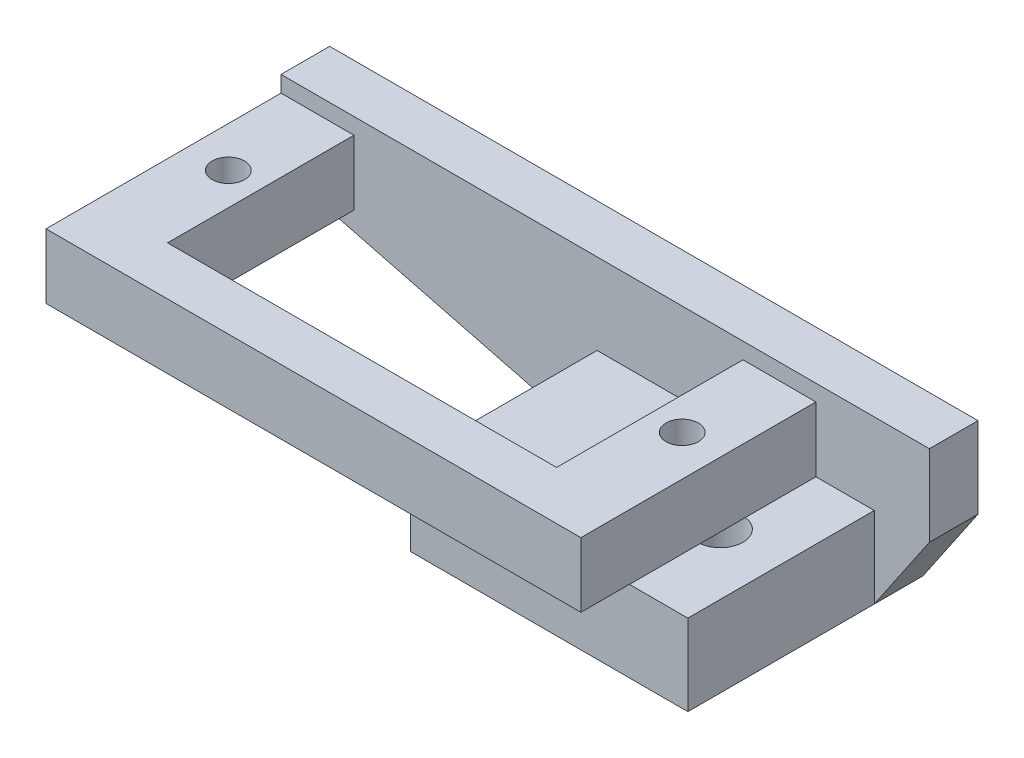
SolidWorks part; units mm, degrees
ref_plane "Спереди" through (0, 0, 0) normal (0, 0, 1) x (1, 0, 0)
ref_plane "Сверху" through (0, 0, 0) normal (0, 1, 0) x (1, 0, 0)
ref_plane "Справа" through (0, 0, 0) normal (1, 0, 0) x (0, 0, -1)
sketch "Эскиз1" plane through (0, 0, 0) normal (0, 0, 1) x (1, 0, 0)
  line L1 (-20, -2.5) -> (20, -2.5)
  line L2 (-20, -2.5) -> (-20, 2.5)
  line L3 (-20, 2.5) -> (20, 2.5)
  line L4 (20, -2.5) -> (20, 2.5)
  line L5 (-20, -2.5) -> (20, 2.5) construction
  line L6 (-20, 2.5) -> (20, -2.5) construction
  point P0 (0, 0)
  dimension "D1" = 40
  dimension "D2" = 5
extrude "Бобышка-Вытянуть1" add sketch "Эскиз1" along normal blind 3
sketch "Эскиз2" plane through (0, 0, 3) normal (0, 0, 1) x (1, 0, 0)
  line L5 (-20, -2.5) -> (-15.5, -2.5)
  line L6 (-20, -2.5) -> (-20, 1.5)
  line L11 (-20, 1.5) -> (-15.5, 1.5)
  line L12 (-15.5, -2.5) -> (-15.5, 1.5)
  line L13 (8.5, -2.5) -> (13, -2.5)
  line L14 (8.5, -2.5) -> (8.5, 1.5)
  line L15 (8.5, 1.5) -> (13, 1.5)
  line L16 (13, -2.5) -> (13, 1.5)
  line L17 (-20, 2.5) -> (-20, -2.5) construction
  point P8 (-20, -7.5)
  dimension "D2" = 24
  dimension "D3" = 4.5
  dimension "D4" = 4.5
  dimension "D5" = 4
extrude "Бобышка-Вытянуть2" add sketch "Эскиз2" along normal blind 11.5
sketch "Эскиз4" plane through (0, 1.5, 0) normal (0, 1, 0) x (1, 0, 0)
  line L0 (-15.5, -8.75) -> (8.5, -8.75) construction
  line L1 (-15.5, -14.5) -> (-15.5, -3) construction
  line L2 (8.5, -14.5) -> (8.5, -3) construction
  line L3 (-3.5, -1.571) -> (-3.5, -13.1628) construction
  circle A0 centre (-17.5, -8.75) radius 1
  circle A1 centre (10.5, -8.75) radius 1
  point P10 (-3.5, -8.75)
  point P11 (-15.5, -9.12)
  point P12 (-15.5, -8.75)
  point P13 (0, 0)
  point P14 (-17.7988, -7.7605)
  dimension "D1" = 2
  dimension "D2" = 28
extrude "Вырез-Вытянуть1" cut sketch "Эскиз4" against normal through all
sketch "Эскиз5" plane through (0, -2.5, 0) normal (0, -1, 0) x (1, 0, 0)
  line L0 (-20, 0) -> (20, 0) construction
  line L1 (16.6, 0) -> (-0.5, 0)
  line L2 (16.6, 0) -> (16.6, 14.5)
  line L3 (16.6, 14.5) -> (-0.5, 14.5)
  line L4 (-0.5, 0) -> (-0.5, 14.5)
  line L5 (8.5, 14.5) -> (13, 14.5) construction
  line L6 (8.5, 14.5) -> (8.5, 3) construction
  circle A0 centre (12.85, 8.75) radius 1.4
  point P10 (-17.5, 8.75)
  point P14 (0, 0)
  dimension "D3" = 2.8
  dimension "D1" = 9
  dimension "D2" = 30.35
  dimension "D4" = 3.75
extrude "Бобышка-Вытянуть3" add sketch "Эскиз5" along normal blind 5
sketch "Эскиз6" plane through (0, 0, 0) normal (0, 0, -1) x (-1, 0, 0)
  line L0 (-20, -2.5) -> (-16.6, -7.5)
  line L1 (20, -2.5) -> (0.5, -7.5)
  line L2 (20, -2.5) -> (0.5, -2.5) construction
  line L3 (0.5, -7.5) -> (0.5, -2.5) construction
  line L4 (-16.6, -7.5) -> (-16.6, -2.5) construction
  line L5 (-16.6, -2.5) -> (-20, -2.5) construction
  line L6 (20, -2.5) -> (0.5, -2.5)
  line L7 (0.5, -7.5) -> (0.5, -2.5)
  line L8 (-16.6, -7.5) -> (-16.6, -2.5)
  line L9 (-16.6, -2.5) -> (-20, -2.5)
extrude "Бобышка-Вытянуть4" add sketch "Эскиз6" against normal up to surface (3 mm away) up to face at (2.3417, -0.3333, 3)
sketch "Эскиз7" plane through (0, -7.5, 0) normal (0, -1, 0) x (1, 0, 0)
  circle A0 centre (12.85, 8.75) radius 1.4 construction
  circle A1 centre (12.85, 8.75) radius 1.4
  circle A2 centre (12.85, 8.75) radius 2.4
  dimension "D1" = 1
extrude "Бобышка-Вытянуть5" add sketch "Эскиз7" along normal blind 0.75
chamfer "Фаска1" distance 1 angle 45 1 edges at (12.85, -7.5, 6.35)
sketch "Эскиз8" plane through (0, 1.5, 0) normal (0, 1, 0) x (1, 0, 0)
  line L0 (13, -14.5) -> (13, -3) construction
  line L1 (-20, -14.5) -> (13, -14.5)
  line L2 (-20, -14.5) -> (-20, -17.5)
  line L3 (-20, -17.5) -> (13, -17.5)
  line L4 (13, -14.5) -> (13, -17.5)
  line L5 (13, -14.5) -> (8.5, -14.5) construction
  point P5 (13, -14.5)
  line M5 (-20, -14.5) -> (-15.5, -14.5)
  dimension "D1" = 3
extrude "Бобышка-Вытянуть11" add sketch "Эскиз8" against normal blind 3.99 contours L4 L1 L2 L3 M5 region at (-3.5, 1.5, 16)
